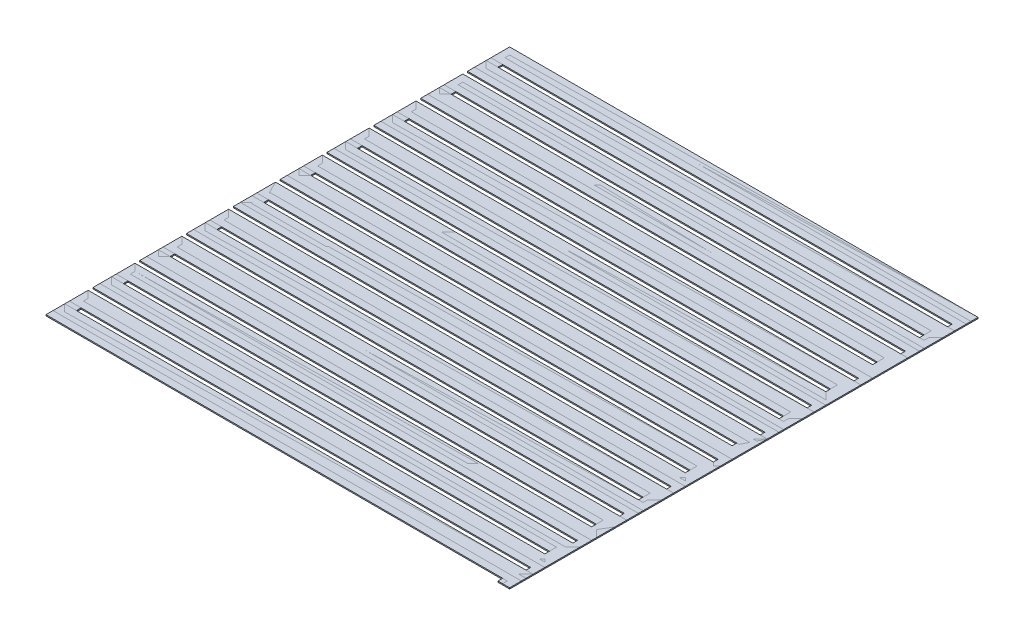
SolidWorks part; units mm, degrees
ref_plane "Front Plane" through (0, 0, 0) normal (0, 0, 1) x (1, 0, 0)
ref_plane "Top Plane" through (0, 0, 0) normal (0, 1, 0) x (1, 0, 0)
ref_plane "Right Plane" through (0, 0, 0) normal (1, 0, 0) x (0, 0, -1)
sketch "Base Guidlines" plane through (0, 0, 0) normal (0, 1, 0) x (1, 0, 0)
  line L0 (-4.5961, 9.2) -> (-4.5961, 8.5)
  line L1 (-10, -10) -> (10, -10)
  line L2 (-10, -10) -> (-10, 10)
  line L3 (-10, 10) -> (10, 10)
  line L4 (10, -10) -> (10, 10)
  line L5 (-10, -10) -> (10, 10) construction
  line L6 (-10, 10) -> (10, -10) construction
  line L7 (-10, 10) -> (10, 10)
  line L8 (-10, 10) -> (-10, 9.2)
  line L9 (-10, 9.2) -> (10, 9.2)
  line L10 (10, 10) -> (10, 9.2)
  line L11 (-4.5961, -9.2) -> (-4.5961, -8.5)
  line L12 (-10, -10) -> (10, -10)
  line L13 (-10, -10) -> (-10, -9.2)
  line L14 (-10, -9.2) -> (10, -9.2)
  line L15 (10, -10) -> (10, -9.2)
  line L17 (-10, -9.2) -> (10, -9.2)
  line L18 (-10, -9.2) -> (-10, -8.5)
  line L19 (-10, -8.5) -> (10, -8.5)
  line L20 (10, -9.2) -> (10, -8.5)
  line L21 (-10, 9.2) -> (10, 9.2)
  line L22 (-10, 9.2) -> (-10, 8.5)
  line L23 (-10, 8.5) -> (10, 8.5)
  line L24 (10, 9.2) -> (10, 8.5)
  point P0 (0, 0)
  dimension "D1" = 20
  dimension "D2" = 20
  dimension "D3" = 0.7
  dimension "D4" = 0.7
sketch "Mirror axis x" plane through (0, 0, 0) normal (0, 1, 0) x (1, 0, 0)
  line L0 (-10, 0) -> (10, 0)
  line L1 (-10, -10) -> (-10, 10) construction
  line L2 (10, -10) -> (10, 10) construction
sketch "TopBlock" plane through (0, 0, 0) normal (0, 1, 0) x (1, 0, 0)
  line L0 (-10, 10) -> (10, -10) construction
  line L1 (-10, 10) -> (-9.7, 10)
  line L2 (-10, 10) -> (-10, 9.7)
  line L3 (10, 9.2) -> (10, 9.5)
  line L4 (-9.7, 10) -> (10, 10)
  line L5 (-9.7, 9.7) -> (-9.7, 9.5)
  line L6 (-10, 9.2) -> (-9.7, 9.2)
  line L7 (-10, 9.2) -> (-10, 9.5)
  line L8 (-9.7, 9.5) -> (9.7, 9.5)
  line L10 (-10, 9.7) -> (-10, 9.5)
  line L11 (-9.7, 9.7) -> (10, 9.7)
  line L12 (10, 9.7) -> (10, 10)
  line L13 (10, -10) -> (10, 10) construction
  line L14 (10, 9.2) -> (9.7, 9.2)
  line L15 (10, 9.5) -> (9.7, 9.5)
  line L24 (9.7, 9.2) -> (-9.7, 9.2)
  dimension "D1" = 0.3
  dimension "D2" = 0.3
extrude "Extruded object" add sketch "TopBlock" along normal blind 0.05
sketch "Mirror axis y" plane through (0, 0, 0) normal (0, 1, 0) x (1, 0, 0)
  line L0 (0, 10) -> (0, -10)
  line L3 (10, 10) -> (-10, 10) construction
  dimension "D1" = 20
sketch "GapandInbetween" plane through (0, 0, 0) normal (0, 1, 0) x (1, 0, 0)
  line L0 (10, 9.2) -> (10, 9)
  line L1 (10, -10) -> (10, 10) construction
  line L2 (10, 9) -> (10, 8.7)
  line L3 (-9.7, 8.5) -> (-9.7, 8.7)
  line L4 (9.7, 9) -> (9.7, 9.2)
  line L5 (-10, 9.2) -> (10, 9.2) construction
  line L6 (9.7, 9.2) -> (10, 9.2)
  line L7 (10, 8.7) -> (-9.7, 8.7)
  line L8 (-10, -10) -> (-10, 10) construction
  line L9 (9.7, 9) -> (-10, 9)
  line L10 (-10, 9) -> (-10, 8.7)
  line L11 (-10, 8.7) -> (-10, 8.5)
  line L12 (-9.7, 8.5) -> (10, 8.5)
  line L13 (-10, 8.5) -> (10, 8.5) construction
  line L14 (-10, 8.5) -> (-10, 8.2)
  line L15 (-10, 8.2) -> (9.7, 8.2)
  line L16 (9.7, 8.2) -> (10, 8.2)
  line L17 (10, 8.2) -> (10, 8.5)
  dimension "D1" = 0.2
  dimension "D2" = 0.3
  dimension "D3" = 0.3
  dimension "D4" = 0.3
  dimension "D5" = 0.3
  dimension "D6" = 19.7
extrude "Boss-Extrude2" add sketch "GapandInbetween" along normal blind 0.05
pattern_linear "LPattern1" count 19 spacing 1 along (0, 0, 1) of "Boss-Extrude2"
sketch "Sketch1" plane through (0, 0, 0) normal (0, 1, 0) x (1, 0, 0)
  line L1 (10, -9.8) -> (10, -10)
  line L2 (9.7, -9.8) -> (9.7, -10)
  line L3 (9.7, -10) -> (10, -10)
  line L4 (10, -9.8) -> (9.7, -9.8)
  line L5 (-10, -9.8) -> (10, -9.8) construction
  dimension "D1" = 0.2
extrude "Boss-Extrude3" add sketch "Sketch1" along normal blind 0.05
sketch "Sketch2" plane through (0, 0, 0) normal (0, 1, 0) x (1, 0, 0)
  line L1 (-10, 10) -> (10, 10)
  line L2 (-10, 10) -> (-10, -10)
  line L3 (-10, -10) -> (10, -10)
  line L4 (10, 10) -> (10, -10)
  dimension "D1" = 20
extrude "Boss-Extrude4" add sketch "Sketch2" along normal blind 0.05 separate body
sketch "Sketch3" plane through (0, 0, 0) normal (0, 1, 0) x (1, 0, 0)
  line L0 (10, -10) -> (10, 10) construction
  line L1 (10, 9.5) -> (-9.5, 9.5)
  line L2 (10, 9.5) -> (10, 9)
  line L3 (10, 9) -> (-9.5, 9)
  line L4 (-9.5, 9.5) -> (-9.5, 9)
  line L5 (10, 10) -> (-10, 10) construction
  line L6 (-10, 10) -> (-10, -10) construction
  dimension "D1" = 0.5
  dimension "D2" = 0.5
  dimension "D3" = 0.5
sketch "Sketch4" plane through (0, 0, 0) normal (0, 1, 0) x (1, 0, 0)
  line L0 (-10, 10) -> (-10, -10) construction
  line L1 (-10, 8.5) -> (9.5, 8.5)
  line L2 (-10, 8.5) -> (-10, 8)
  line L3 (-10, 8) -> (9.5, 8)
  line L4 (9.5, 8.5) -> (9.5, 8)
  line L5 (10, 9) -> (-9.5, 9) construction
  line L6 (10, -10) -> (10, 10) construction
  dimension "D1" = 0.5
  dimension "D2" = 0.5
  dimension "D3" = 0.5
extrude "Cut-Extrude3" cut sketch "Sketch3" along normal blind 0.05
extrude "Cut-Extrude5" cut sketch "Sketch4" along normal blind 0.05
pattern_linear "LPattern2" count 10 spacing 2 along (0, 0, 1) of "Cut-Extrude3"
pattern_linear "LPattern3" count 10 spacing 2 along (0, 0, 1) of "Cut-Extrude5"
